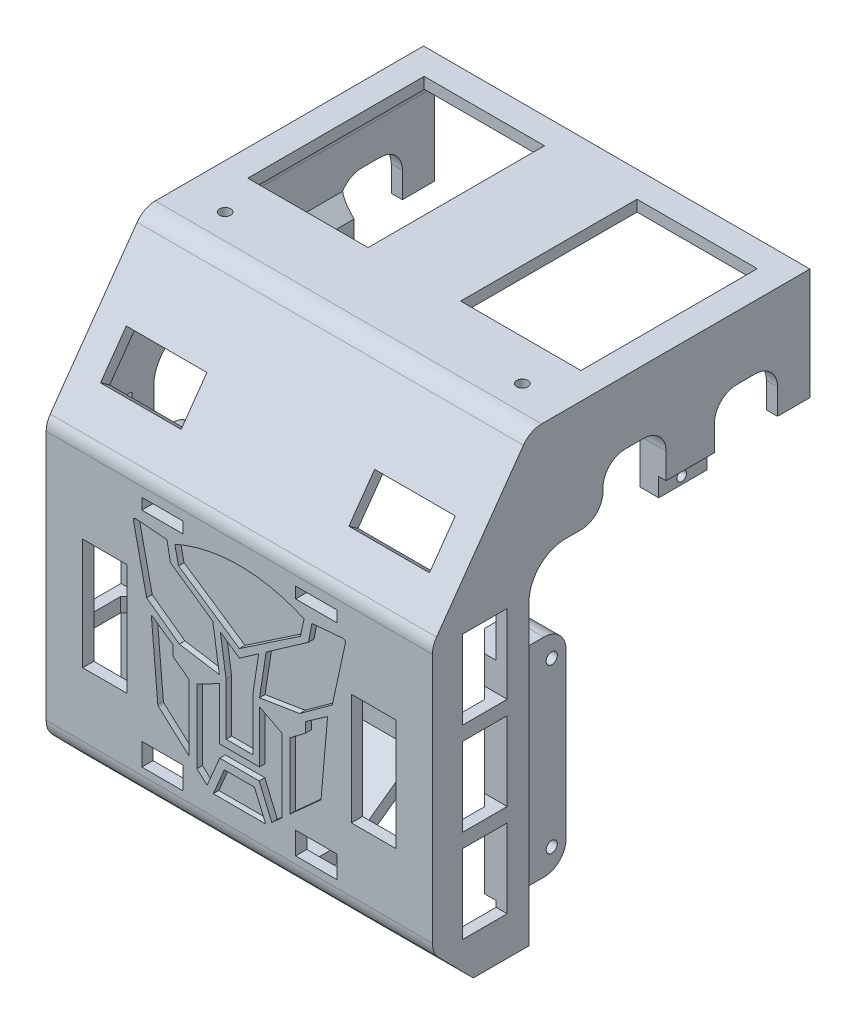
SolidWorks part; units mm, degrees
ref_plane "前视基准面" through (0, 0, 0) normal (0, 0, 1) x (1, 0, 0)
ref_plane "上视基准面" through (0, 0, 0) normal (0, 1, 0) x (1, 0, 0)
ref_plane "右视基准面" through (0, 0, 0) normal (1, 0, 0) x (0, 0, -1)
other "Configuration Table"
sketch "草图1" plane through (0, 0, 0) normal (1, 0, 0) x (0, 0, -1)
  line L0 (-79.1155, 42.8793) -> (-52.828, 80)
  line L1 (-53.1155, -40) -> (-53.1155, -28)
  line L10 (-68.1155, -40) -> (-79.1155, -28.8582)
  line L13 (-53.1155, 28) -> (-53.1155, 50)
  line L16 (-52.828, 80) -> (22.4941, 80)
  line L17 (-53.1155, -40) -> (-68.1155, -40)
  line L18 (-79.1155, 42.8793) -> (-79.1155, -28.8582)
  line L22 (-53.1155, 50) -> (22.4941, 50)
  line L23 (22.4941, 50) -> (22.4941, 80)
  line L24 (-53.1155, 28) -> (-53.1155, -28)
  circle A0 centre (-45, -35) radius 5 construction
  dimension "D1" = 26
  dimension "D2" = 90
  dimension "D3" = 30
extrude "凸台-拉伸1" add sketch "草图1" along normal blind 104
sketch "草图6" plane through (0, 0, 53.1155) normal (0, 0, -1) x (-1, 0, 0)
  line L0 (-104, 28) -> (0, 28)
  line L1 (0, 28) -> (0, -28)
  line L2 (0, -28) -> (-104, -28)
  line L3 (-104, -28) -> (-104, 28)
shell "抽壳6" thickness 3 removed face at (52, 50, 15.3107) removed face at (52, 5, 53.1155) removed face at (52, 65, -22.4941)
extrude "凸台-拉伸3" add sketch "草图6" along normal blind 12
sketch "草图7" plane through (0, 0, 41.1155) normal (0, 0, -1) x (-1, 0, 0)
  line L1 (-12, -34.2105) -> (-92, -34.2105)
  line L2 (-12, -34.2105) -> (-12, 34.2105)
  line L3 (-12, 34.2105) -> (-92, 34.2105)
  line L4 (-92, -34.2105) -> (-92, 34.2105)
  line L5 (-52, 34.2105) -> (-52, -34.2105) construction
  line L6 (-12, 0) -> (-92, 0) construction
  point P0 (-52, 0)
extrude "切除-拉伸4" cut sketch "草图7" against normal blind 12
chamfer "倒角1" distance 9 angle 45 2 edges at (3, 0, 53.1155) (101, 0, 53.1155)
sketch "草图8" plane through (104, 0, 0) normal (1, 0, 0) x (0, 0, -1)
  circle A0 centre (-45, 22) radius 1.5
  circle A1 centre (-45, -22) radius 1.5
extrude "切除-拉伸5" cut sketch "草图8" against normal through all
sketch "草图9" plane through (104, 0, 0) normal (1, 0, 0) x (0, 0, -1)
  line L0 (-53.1155, 28) -> (-41.1155, 28)
  line L1 (-41.1155, 28) -> (-41.1155, -28)
  line L2 (-41.1155, -28) -> (-53.1155, -28)
  line L3 (-53.1155, -40) -> (-53.1155, -28) construction
  line L4 (-41.1155, -28) -> (-53.1155, -28) construction
  line L5 (-53.1155, -28) -> (-53.1155, 28)
extrude "切除-拉伸6" cut sketch "草图9" against normal blind 2
sketch "草图10" plane through (0, 0, 0) normal (-1, 0, 0) x (0, 0, 1)
  line L0 (41.1155, 28) -> (53.1155, 28)
  line L1 (53.1155, 28) -> (53.1155, -28)
  line L2 (53.1155, -28) -> (41.1155, -28)
  line L3 (41.1155, -28) -> (41.1155, 28)
extrude "切除-拉伸7" cut sketch "草图10" against normal blind 2
sketch "草图14" plane through (0, 80, 0) normal (0, 1, 0) x (1, 0, 0)
  line L0 (52, 25.6993) -> (52, 16.9484) construction
  circle A0 centre (92, -42.9268) radius 1.5
  circle A1 centre (12, -42.9268) radius 1.5
  dimension "D1" = 40
extrude "切除-拉伸8" cut sketch "草图14" against normal blind 10
sketch "草图15" plane through (0, 51.6356, 72.9147) normal (0, 0.5779, 0.8161) x (1, 0, 0)
  line L0 (52, 31.6659) -> (52, 23.5661) construction
  line L2 (7.7161, 13.2579) -> (29.4161, 13.2579)
  line L3 (96.2839, 1.2579) -> (74.5839, 1.2579)
  line L4 (96.2839, 1.2579) -> (96.2839, 13.2579)
  line L5 (96.2839, 13.2579) -> (74.5839, 13.2579)
  line L6 (74.5839, 1.2579) -> (74.5839, 13.2579)
  line L9 (29.4161, 1.2579) -> (29.4161, 13.2579)
  line L10 (7.7161, 1.2579) -> (29.4161, 1.2579)
  line L11 (7.7161, 1.2579) -> (7.7161, 13.2579)
extrude "切除-拉伸9" cut sketch "草图15" against normal blind 10
sketch "草图16" plane through (0, 0, 79.1155) normal (0, 0, 1) x (1, 0, 0)
  line L0 (36.8223, 35.4631) -> (36.8223, 38.4631)
  line L1 (36.8223, 35.4631) -> (25.7536, 35.4631)
  line L2 (9.831, 20.7544) -> (21.831, 20.7544)
  line L3 (94.169, -9.2456) -> (82.169, -9.2456)
  line L4 (94.169, -9.2456) -> (94.169, 20.7544)
  line L5 (94.169, 20.7544) -> (82.169, 20.7544)
  line L6 (82.169, -9.2456) -> (82.169, 20.7544)
  line L7 (88.169, 20.7544) -> (88.169, -9.2456) construction
  line L8 (94.169, 5.7544) -> (82.169, 5.7544) construction
  line L9 (21.831, -9.2456) -> (21.831, 20.7544)
  line L10 (9.831, -9.2456) -> (21.831, -9.2456)
  line L11 (9.831, -9.2456) -> (9.831, 20.7544)
  line L12 (36.8223, 38.4631) -> (25.7536, 38.4631)
  line L13 (25.7536, 38.4631) -> (25.7536, 35.4631)
  line L16 (78.2423, 35.4631) -> (67.1736, 35.4631)
  line L17 (78.2423, 35.4631) -> (78.2423, 38.4631)
  line L18 (78.2423, 38.4631) -> (67.1736, 38.4631)
  line L25 (78.2423, -18.442) -> (78.2423, -24.442)
  line L28 (67.1736, 38.4631) -> (67.1736, 35.4631)
  line L31 (78.2423, -24.442) -> (67.1736, -24.442)
  line L32 (67.1736, -24.442) -> (67.1736, -18.442)
  line L33 (78.2423, -18.442) -> (67.1736, -18.442)
  line L34 (36.8264, -24.442) -> (36.8264, -18.442)
  line L35 (36.8264, -24.442) -> (25.7577, -24.442)
  line L36 (25.7577, -18.442) -> (25.7577, -24.442)
  line L37 (36.8264, -18.442) -> (25.7577, -18.442)
  point P1 (88.169, 5.7544)
  point P24 (52, -21.442)
extrude "切除-拉伸10" cut sketch "草图16" against normal blind 10
sketch "草图17" plane through (0, 80, 0) normal (0, 1, 0) x (1, 0, 0)
  line L0 (52, 25.6993) -> (52, 22.3046) construction
  line L2 (39.5379, -31.9885) -> (7.1533, -31.9885)
  line L3 (64.4621, 15.5041) -> (96.8467, 15.5041)
  line L4 (64.4621, 15.5041) -> (64.4621, -31.9885)
  line L5 (64.4621, -31.9885) -> (96.8467, -31.9885)
  line L6 (96.8467, 15.5041) -> (96.8467, -31.9885)
  line L7 (80.6544, -31.9885) -> (80.6544, 15.5041) construction
  line L8 (64.4621, -8.2422) -> (96.8467, -8.2422) construction
  line L9 (7.1533, 15.5041) -> (7.1533, -31.9885)
  line L10 (39.5379, 15.5041) -> (7.1533, 15.5041)
  line L11 (39.5379, 15.5041) -> (39.5379, -31.9885)
  point P1 (80.6544, -8.2422)
extrude "切除-拉伸11" cut sketch "草图17" against normal blind 10
sketch "草图19" plane through (104, 0, 0) normal (1, 0, 0) x (0, 0, -1)
  line L0 (-70.9745, -4.582) -> (-70.9745, 16.6095)
  line L3 (-58.9745, 20.418) -> (-70.9745, 20.418)
  line L4 (-58.9745, 20.418) -> (-58.9745, 41.6095)
  line L5 (-58.9745, 41.6095) -> (-70.9745, 41.6095)
  line L6 (-70.9745, 20.418) -> (-70.9745, 41.6095)
  line L9 (-58.9745, -4.582) -> (-58.9745, 16.6095)
  line L10 (-58.9745, 16.6095) -> (-70.9745, 16.6095)
  line L11 (-58.9745, -4.582) -> (-70.9745, -4.582)
  line L12 (-70.9745, -29.582) -> (-70.9745, -8.3905)
  line L13 (-58.9745, -29.582) -> (-58.9745, -8.3905)
  line L14 (-58.9745, -29.582) -> (-70.9745, -29.582)
  line L15 (-58.9745, -8.3905) -> (-70.9745, -8.3905)
  point P0 (-69.9745, 31.0137)
extrude "切除-拉伸12" cut sketch "草图19" against normal through all
fillet "圆角1" radius 9.8 2 edges at (1.5, 50, 53.1155) (102.5, 50, 53.1155)
sketch "草图20" plane through (104, 0, 0) normal (1, 0, 0) x (0, 0, -1)
  line L0 (-33.183, 48.519) -> (-33.183, 62.8878)
  line L1 (-3.183, 48.519) -> (-3.183, 62.8878)
  line L2 (-33.183, 62.8878) -> (-16.202, 62.8878)
  line L3 (-16.202, 62.8878) -> (-16.202, 48.519)
  line L4 (-33.183, 48.519) -> (-16.202, 48.519)
  line L9 (-3.183, 62.8878) -> (13.798, 62.8878)
  line L10 (13.798, 62.8878) -> (13.798, 48.519)
  line L11 (-3.183, 48.519) -> (13.798, 48.519)
extrude "切除-拉伸13" cut sketch "草图20" against normal through all
fillet "圆角3" radius 6 13 edges at (52, -28.8582, 79.1155) (52, 42.8793, 79.1155) (52, 80, 52.828) (102.5, 62.8878, -13.798) (102.5, 62.8878, 3.183) (102.5, 62.8878, 16.202) (102.5, 62.8878, 33.183) (102.5, 50, 33.183) (1.5, 62.8878, 33.183) (1.5, 62.8878, 16.202) (1.5, 62.8878, 3.183) (1.5, 62.8878, -13.798) (1.5, 50, 33.183)
fillet "圆角4" radius 6 4 edges at (7, -28, 41.1155) (7, 28, 41.1155) (97, -28, 41.1155) (97, 28, 41.1155)
sketch "草图24" plane through (0, 0, 79.1155) normal (0, 0, 1) x (1, 0, 0)
  line L0 (52, 17.3921) -> (52, -2.8175) construction
  line L4 (67.6, 7.2873) -> (36.4, 7.2873) construction
  line L6 (47.9916, -13.9653) -> (44.9908, -21.0348)
  line L7 (44.9908, -21.0348) -> (59.0925, -21.0348)
  line L8 (59.0925, -21.0348) -> (56.0916, -13.9653)
  line L9 (56.0916, -13.9653) -> (47.9916, -13.9653)
  line L10 (74.0232, -7.7112) -> (75.7805, 12.3758)
  line L11 (75.7805, 12.3758) -> (69.8826, 8.246)
  line L12 (69.8826, 8.246) -> (69.8826, 5.546)
  line L13 (69.8826, 5.546) -> (65.6422, 2.3261)
  line L14 (65.6422, 2.3261) -> (65.6422, -15.4743)
  line L15 (65.6422, -15.4743) -> (73.8269, -8.1048)
  line L16 (57.4416, -8.5653) -> (46.6416, -8.5653)
  line L17 (46.6416, -8.5653) -> (46.6416, 5.4597)
  line L18 (46.6416, 5.4597) -> (40.5785, 2.3261)
  line L19 (40.5785, 2.3261) -> (40.5785, -17.3989)
  line L20 (40.5785, -17.3989) -> (43.3319, -19.878)
  line L21 (43.3319, -19.878) -> (46.7312, -11.8696)
  line L22 (46.7312, -11.8696) -> (57.3521, -11.8696)
  line L23 (57.3521, -11.8696) -> (60.7514, -19.878)
  line L24 (60.7514, -19.878) -> (63.5048, -17.3989)
  line L25 (63.5048, -17.3989) -> (63.5048, 2.3261)
  line L26 (63.5048, 2.3261) -> (57.4416, 5.4597)
  line L27 (57.4416, 5.4597) -> (57.4416, -8.5653)
  line L28 (30.2564, -8.1048) -> (38.4411, -15.4743)
  line L29 (38.4411, -15.4743) -> (38.4411, 2.3261)
  line L30 (38.4411, 2.3261) -> (34.2007, 5.546)
  line L31 (34.2007, 5.546) -> (34.2007, 8.246)
  line L32 (34.2007, 8.246) -> (28.3028, 12.3758)
  line L33 (28.3028, 12.3758) -> (30.0601, -7.7112)
  line L34 (52.0416, 14.0847) -> (46.881, 17.6982)
  line L35 (46.881, 17.6982) -> (48.4416, 7.3347)
  line L36 (48.4416, 7.3347) -> (48.4416, -6.6153)
  line L37 (48.4416, -6.6153) -> (55.6416, -6.6153)
  line L38 (55.6416, -6.6153) -> (55.6416, 7.3347)
  line L39 (55.6416, 7.3347) -> (57.2023, 17.6982)
  line L40 (57.2023, 17.6982) -> (52.0416, 14.0847)
  line L41 (79.9395, 32.6668) -> (71.5575, 31.9544)
  line L42 (71.5575, 31.9544) -> (70.6206, 27.0938)
  line L43 (70.6206, 27.0938) -> (59.2259, 19.1152)
  line L44 (59.2259, 19.1152) -> (57.4416, 7.552)
  line L45 (57.4416, 7.552) -> (68.2416, 9.2847)
  line L46 (68.2416, 9.2847) -> (77.0402, 15.686)
  line L47 (77.0402, 15.686) -> (80.5766, 31.9415)
  line L48 (23.5067, 31.9415) -> (27.0431, 15.686)
  line L49 (27.0431, 15.686) -> (35.8416, 9.2847)
  line L50 (35.8416, 9.2847) -> (46.6416, 7.552)
  line L51 (46.6416, 7.552) -> (44.8574, 19.1152)
  line L52 (44.8574, 19.1152) -> (33.4627, 27.0938)
  line L53 (33.4627, 27.0938) -> (32.5258, 31.9544)
  line L54 (32.5258, 31.9544) -> (24.1438, 32.6668)
  line L55 (35.6267, 27.4067) -> (52.0416, 16.3347)
  line L56 (52.0416, 16.3347) -> (68.4566, 27.4067)
  line L57 (68.4566, 27.4067) -> (69.4445, 31.9476)
  line L58 (34.6382, 31.9504) -> (35.6267, 27.4067)
  line L59 (52.1388, 7.4453) -> (175.7126, 7.4453) construction
  line L60 (52.1388, 7.4453) -> (52.1388, 166.2164) construction
  arc A0 (73.8269, -8.1048) -> (74.0232, -7.7112) centre (73.4254, -7.6589) ccw
  arc A1 (30.0601, -7.7112) -> (30.2564, -8.1048) centre (30.6579, -7.6589) ccw
  arc A2 (80.5766, 31.9415) -> (79.9395, 32.6668) centre (79.9903, 32.069) ccw
  arc A3 (24.1438, 32.6668) -> (23.5067, 31.9415) centre (24.093, 32.069) ccw
  arc A4 (69.4445, 31.9476) -> (34.6382, 31.9504) centre (52.0382, -6.6225) ccw
extrude "切除-拉伸14" cut sketch "草图24" against normal blind 1.5
sketch "草图25" plane through (92, 0, 0) normal (-1, 0, 0) x (0, 0, 1)
  circle A0 centre (45, 22) radius 2.1
  circle A1 centre (45, -22) radius 2.1
extrude "切除-拉伸15" cut sketch "草图25" against normal blind 3
sketch "草图26" plane through (12, 0, 0) normal (1, 0, 0) x (0, 0, -1)
  circle A0 centre (-45, 22) radius 2.1
  circle A1 centre (-45, -22) radius 2.1
extrude "切除-拉伸16" cut sketch "草图26" against normal blind 3
sketch "草图27" plane through (0, -40, 0) normal (0, -1, 0) x (1, 0, 0)
  line L0 (52, 65.6077) -> (52, 63.2174) construction
  line L2 (62.0104, 57.0092) -> (92.0104, 57.0092)
  line L3 (41.9896, 62.5929) -> (11.9896, 62.5929)
  line L4 (41.9896, 62.5929) -> (41.9896, 57.0092)
  line L5 (41.9896, 57.0092) -> (11.9896, 57.0092)
  line L6 (11.9896, 62.5929) -> (11.9896, 57.0092)
  line L7 (26.9896, 57.0092) -> (26.9896, 62.5929) construction
  line L8 (41.9896, 59.801) -> (11.9896, 59.801) construction
  line L9 (92.0104, 62.5929) -> (92.0104, 57.0092)
  line L10 (62.0104, 62.5929) -> (92.0104, 62.5929)
  line L11 (62.0104, 62.5929) -> (62.0104, 57.0092)
  point P1 (26.9896, 59.801)
extrude "切除-拉伸17" cut sketch "草图27" against normal blind 10
sketch "草图28" plane through (0, 0, 53.1155) normal (0, 0, -1) x (-1, 0, 0)
  line L0 (-101, -37) -> (-3, -37) construction
  line L2 (-3, -30.9292) -> (-101, -30.9292)
  line L3 (-3, -30.9292) -> (-3, -43.0708)
  line L4 (-3, -43.0708) -> (-101, -43.0708)
  line L5 (-101, -30.9292) -> (-101, -43.0708)
  line L6 (-52, -43.0708) -> (-52, -30.9292) construction
  line L7 (-3, -37) -> (-101, -37) construction
  point P4 (-52, -37)
extrude "切除-拉伸18" cut sketch "草图28" against normal blind 13.75
sketch "草图31" plane through (0, 0, 66.8655) normal (0, 0, -1) x (-1, 0, 0)
  line L0 (-101, -36.996) -> (-3, -36.996) construction
  line L1 (-52, -36.996) -> (-52, -30.4643) construction
  line L2 (-62, -36.996) -> (-42, -36.996)
  line L3 (-42, -36.996) -> (-42, -32.996)
  line L5 (-42, -32.996) -> (-62, -32.996)
  line L6 (-62, -36.996) -> (-62, -32.996)
  point P13 (-52, -27.6268)
  point P14 (-52, -36.996)
extrude "凸台-拉伸5" add sketch "草图31" against normal up to surface and the other way blind 10 contours L5 L6 L2 L3 up to face at (52, -32.3114, 71.4905)
sketch "草图32" plane through (42, 0, 0) normal (-1, 0, 0) x (0, 0, 1)
  line L6 (56.8655, -32.996) -> (56.8655, -36.996)
  line L7 (56.8655, -32.996) -> (41.124, -21.6815)
  line L8 (41.124, -21.6815) -> (41.1155, -11.6815)
  line L11 (41.1155, -22) -> (41.1155, 22) construction
  line L12 (41.1155, -11.6815) -> (37.1155, -11.6815)
  line L13 (37.1155, -11.6815) -> (37.1155, -22.8004)
  line L14 (37.1155, -22.8004) -> (56.8655, -36.996)
  arc A0 (41.1155, -22) -> (47.1155, -28) centre (47.1155, -22) ccw construction
extrude "凸台-拉伸6" add sketch "草图32" against normal blind 20
fillet "圆角9" radius 3 1 edges at (52, -36.996, 66.8655)
sketch "草图33" plane through (102, 0, 0) normal (1, 0, 0) x (0, 0, -1)
  line L6 (-16.202, 50) -> (-16.202, 55)
  line L7 (-16.202, 50) -> (-16.202, 45)
  line L8 (-16.202, 55) -> (-3.183, 55)
  line L9 (-3.183, 56.8878) -> (-3.183, 50) construction
  line L10 (-3.183, 55) -> (-3.183, 45)
  line L11 (-16.202, 45) -> (-3.183, 45)
  circle A0 centre (-10, 47) radius 1.3
extrude "凸台-拉伸7" add sketch "草图33" against normal blind 5
sketch "草图35" plane through (2, 0, 0) normal (-1, 0, 0) x (0, 0, 1)
  line L0 (3.183, 50) -> (3.183, 55)
  line L1 (3.183, 56.8878) -> (3.183, 50) construction
  line L2 (3.183, 55) -> (16.202, 55)
  line L3 (16.202, 55) -> (16.202, 45)
  line L4 (16.202, 45) -> (3.183, 45)
  line L5 (3.183, 45) -> (3.183, 50)
  circle A0 centre (10, 47) radius 1.3
extrude "凸台-拉伸8" add sketch "草图35" against normal blind 5
chamfer "倒角2" distance 5 angle 45 2 edges at (3, 55, 9.6925) (101, 55, 9.6925)
fillet "圆角10" radius 5 2 edges at (101, 77, 14.3912) (3, 77, 14.3912)
